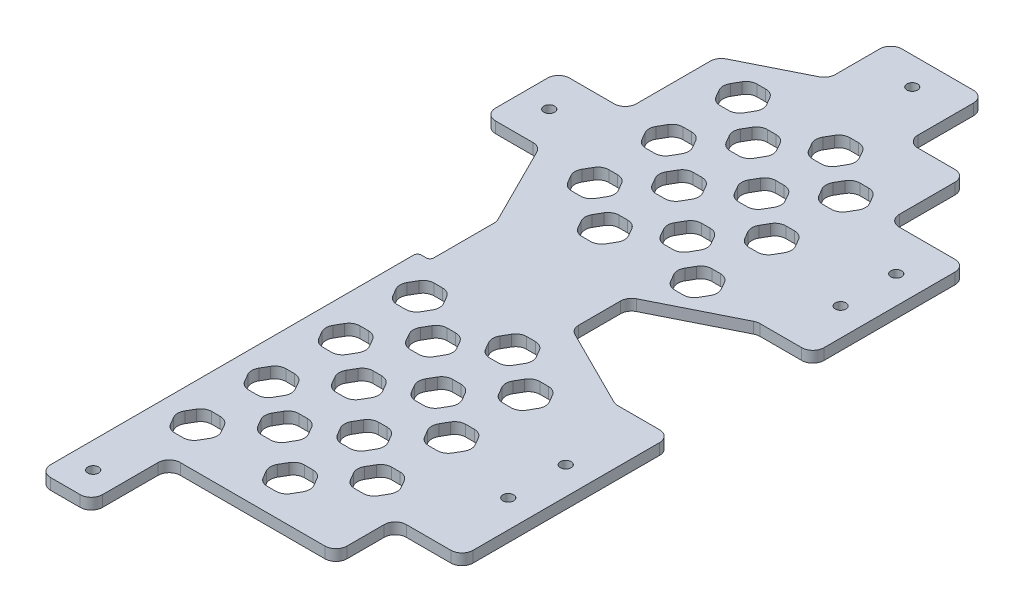
SolidWorks part; units mm, degrees
material "轻木"
ref_plane "前视基准面" through (0, 0, 0) normal (0, 0, 1) x (1, 0, 0)
ref_plane "上视基准面" through (0, 0, 0) normal (0, 1, 0) x (1, 0, 0)
ref_plane "右视基准面" through (0, 0, 0) normal (1, 0, 0) x (0, 0, -1)
other "Configuration Table"
sketch "草图1" plane through (0, 0, 0) normal (0, 1, 0) x (1, 0, 0)
  line L0 (-35.15, -92.5) -> (-35.15, 92.5) construction
  line L1 (-50.15, -107.5) -> (50.15, -107.5) construction
  line L2 (-50.15, -107.5) -> (-50.15, 107.5) construction
  line L3 (-50.15, 107.5) -> (50.15, 107.5) construction
  line L4 (50.15, -107.5) -> (50.15, 107.5) construction
  line L5 (-50.15, -107.5) -> (50.15, 107.5) construction
  line L6 (-50.15, 107.5) -> (50.15, -107.5) construction
  line L7 (-35.15, 92.5) -> (35.15, 92.5) construction
  line L8 (35.15, -92.5) -> (35.15, 92.5) construction
  line L9 (-35.15, -92.5) -> (35.15, -92.5) construction
  line L10 (-29.85, -107.5) -> (-29.85, -2.5) construction
  line L11 (-9.85, -92.5) -> (-9.85, -107.5) construction
  line L12 (-29.85, -2.5) -> (-25.15, -2.5) construction
  line L13 (-25.15, -2.5) -> (-25.15, 12.5) construction
  line L14 (-35.15, 32.5) -> (-50.15, 32.5) construction
  line L15 (-25.15, 12.5) -> (-35.15, 32.5) construction
  line L16 (15.15, 12.5) -> (15.15, -2.5) construction
  line L17 (15.15, -2.5) -> (35.15, -12.5) construction
  line L18 (35.15, -12.5) -> (50.15, -12.5) construction
  line L19 (15.15, 12.5) -> (35.15, 22.5) construction
  line L20 (35.15, 22.5) -> (50.15, 22.5) construction
  line L21 (-54.2695, 5) -> (53.0339, 5) construction
  line L22 (16.15, 107.5) -> (16.15, 92.5) construction
  line L23 (35.15, 68.5) -> (50.15, 68.5) construction
  line L24 (50.15, 65.5) -> (29.15, 65.5)
  line L25 (-50.15, 82.5) -> (-35.15, 82.5) construction
  line L26 (-35.15, 82.5) -> (-15.15, 92.5) construction
  line L27 (35.15, -73.5) -> (50.15, -73.5) construction
  line L28 (-12.85, -86.5) -> (-12.85, -107.5)
  line L29 (-12.85, -107.5) -> (-26.85, -107.5)
  line L30 (-26.85, -107.5) -> (-26.85, -5.5)
  line L31 (-26.85, -5.5) -> (-23.4729, -5.5)
  line L32 (-23.4729, -5.5) -> (-23.4729, 12.5)
  line L33 (-23.4729, 12.5) -> (-35.15, 35.8541)
  line L34 (-35.15, 35.8541) -> (-50.15, 35.8541)
  line L35 (-50.15, 35.8541) -> (-50.15, 55.8541)
  line L36 (-50.15, 55.8541) -> (-32.15, 55.8541)
  line L39 (-12.15, 90.6459) -> (-12.15, 107.5)
  line L40 (-12.15, 107.5) -> (13.15, 107.5)
  line L41 (13.15, 107.5) -> (13.15, 86.5)
  line L44 (50.15, 65.5) -> (50.15, 24.1771)
  line L45 (50.15, 24.1771) -> (35.15, 24.1771)
  line L46 (-25.15, 12.5) -> (15.15, 12.5) construction
  line L47 (-25.15, -2.5) -> (15.15, -2.5) construction
  line L48 (35.15, 24.1771) -> (11.7959, 12.5)
  line L49 (11.7959, 12.5) -> (11.7959, -2.5)
  line L50 (11.7959, -2.5) -> (35.15, -14.1771)
  line L51 (35.15, -14.1771) -> (50.15, -14.1771)
  line L52 (50.15, -14.1771) -> (50.15, -70.5)
  line L53 (50.15, -70.5) -> (32.15, -70.5)
  line L54 (32.15, -70.5) -> (32.15, -86.5)
  line L55 (32.15, -86.5) -> (-12.85, -86.5)
  line L56 (-15.15, 92.5) -> (-15.15, 107.5) construction
  line L57 (-32.15, 55.8541) -> (-32.15, 80.6459)
  line L58 (-32.15, 80.6459) -> (-12.15, 90.6459)
  line L59 (29.15, 65.5) -> (29.15, 86.5)
  line L60 (29.15, 86.5) -> (13.15, 86.5)
  point P0 (0, 0)
  dimension "D1" = 215
  dimension "D2" = 100.3
  dimension "D4" = 105
  dimension "D5" = 5.3
  dimension "D6" = 20
  dimension "D7" = 4.7
  dimension "D8" = 35
  dimension "D9" = 15
  dimension "D10" = 35
  dimension "D11" = 15
  dimension "D12" = 20
  dimension "D13" = 7.5
  dimension "D14" = 19
  dimension "D15" = 25
  dimension "D16" = 20
  dimension "D17" = 19
  dimension "D18" = 3
  dimension "D19" = 3
  dimension "D20" = 6
  dimension "D21" = 3
  dimension "D22" = 3
  dimension "D23" = 3
  dimension "D24" = 3
  dimension "D25" = 3
  dimension "D26" = 24
  dimension "D27" = 3
  dimension "D28" = 3
  dimension "D29" = 3
  dimension "D30" = 20
  dimension "D31" = 3
  dimension "D32" = 6
  dimension "D33" = 3
  dimension "D34" = 6
  dimension "D3" = 15
extrude "凸台-拉伸1" add sketch "草图1" along normal blind 3
fillet "圆角1" radius 3 25 edges at (32.15, 1.5, 70.5) (-12.85, 1.5, 86.5) (-12.85, 1.5, 107.5) (-26.85, 1.5, 107.5) (-23.4729, 1.5, -12.5) (-35.15, 1.5, -35.8541) (-50.15, 1.5, -35.8541) (-50.15, 1.5, -55.8541) (-12.15, 1.5, -107.5) (13.15, 1.5, -107.5) (50.15, 1.5, -24.1771) (35.15, 1.5, -24.1771) (11.7959, 1.5, -12.5) (11.7959, 1.5, 2.5) (35.15, 1.5, 14.1771) (50.15, 1.5, 14.1771) (32.15, 1.5, 86.5) (50.15, 1.5, 70.5) (29.15, 1.5, -86.5) (50.15, 1.5, -65.5) (-32.15, 1.5, -55.8541) (-32.15, 1.5, -80.6459) (-12.15, 1.5, -90.6459) (13.15, 1.5, -86.5) (29.15, 1.5, -65.5)
fillet "圆角2" radius 1 2 edges at (-26.85, 1.5, 5.5) (-23.4729, 1.5, 5.5)
sketch "草图2" plane through (0, 3, 0) normal (0, 1, 0) x (1, 0, 0)
  line L0 (-27.2327, 100) -> (45.5671, 100) construction
  line L1 (-42.65, 71.8095) -> (-42.65, -83.5842) construction
  line L2 (42.65, 78.6701) -> (42.65, -87.3285) construction
  line L3 (-44.3254, -100) -> (0, -100) construction
  line L4 (-23.85, -107.5) -> (-15.85, -107.5) construction
  line L5 (50.15, -67.5) -> (50.15, -17.1771) construction
  line L6 (-50.15, 52.8541) -> (-50.15, 38.8541) construction
  line L7 (10.15, 107.5) -> (-9.15, 107.5) construction
  line L8 (-26.85, -6.5) -> (-26.85, -104.5) construction
  line L9 (35.15, -70.5) -> (47.15, -70.5) construction
  line L10 (35.8582, 24.1771) -> (47.15, 24.1771) construction
  line L11 (-47.15, 35.8541) -> (-37.0041, 35.8541) construction
  line L12 (13.15, 89.5) -> (13.15, 104.5) construction
  circle A0 centre (-19.85, -100) radius 1.45
  circle A1 centre (42.65, -50.5) radius 1.45
  circle A2 centre (42.65, -35) radius 1.45
  circle A3 centre (-42.65, 45.8541) radius 1.45
  circle A4 centre (1.15, 100) radius 1.45
  circle A5 centre (42.65, 54.1771) radius 1.45
  circle A6 centre (42.65, 39.1771) radius 1.45
  dimension "D5" = 2.9
  dimension "D6" = 7
  dimension "D7" = 20
  dimension "D8" = 15.5
  dimension "D9" = 15
  dimension "D10" = 15
  dimension "D12" = 12
  dimension "D1" = 7.5
  dimension "D2" = 7.5
  dimension "D3" = 7.5
  dimension "D4" = 7.5
  dimension "D11" = 10
extrude "切除-拉伸1" cut sketch "草图2" against normal through all
sketch "草图3" plane through (0, 3, 0) normal (0, 1, 0) x (1, 0, 0)
  line L0 (11.4836, 74.7429) -> (8.5968, 79.7429)
  line L1 (-13.5164, 74.7429) -> (-16.4032, 79.7429)
  line L2 (-16.4032, 79.7429) -> (-22.1767, 79.7429)
  line L3 (-22.1767, 79.7429) -> (-25.0634, 74.7429)
  line L4 (-25.0634, 74.7429) -> (-22.1767, 69.7429)
  line L5 (-22.1767, 69.7429) -> (-16.4032, 69.7429)
  line L6 (-16.4032, 69.7429) -> (-13.5164, 74.7429)
  line L7 (-1.527, 65.5092) -> (-4.4137, 70.5092)
  line L8 (-4.4137, 70.5092) -> (-10.1872, 70.5092)
  line L9 (-10.1872, 70.5092) -> (-13.074, 65.5092)
  line L10 (-13.074, 65.5092) -> (-10.1872, 60.5092)
  line L11 (-10.1872, 60.5092) -> (-4.4137, 60.5092)
  line L12 (-4.4137, 60.5092) -> (-1.527, 65.5092)
  line L13 (8.5968, 79.7429) -> (2.8233, 79.7429)
  line L14 (2.8233, 79.7429) -> (-0.0634, 74.7429)
  line L15 (-0.0634, 74.7429) -> (2.8233, 69.7429)
  line L16 (2.8233, 69.7429) -> (8.5968, 69.7429)
  line L17 (8.5968, 69.7429) -> (11.4836, 74.7429)
  line L18 (23.473, 65.5092) -> (20.5863, 70.5092)
  line L19 (20.5863, 70.5092) -> (14.8128, 70.5092)
  line L20 (14.8128, 70.5092) -> (11.926, 65.5092)
  line L21 (11.926, 65.5092) -> (14.8128, 60.5092)
  line L22 (14.8128, 60.5092) -> (20.5863, 60.5092)
  line L23 (20.5863, 60.5092) -> (23.473, 65.5092)
  line L24 (11.4836, 54.7429) -> (8.5968, 59.7429)
  line L25 (8.5968, 59.7429) -> (2.8233, 59.7429)
  line L26 (2.8233, 59.7429) -> (-0.0634, 54.7429)
  line L27 (-0.0634, 54.7429) -> (2.8233, 49.7429)
  line L28 (2.8233, 49.7429) -> (8.5968, 49.7429)
  line L29 (8.5968, 49.7429) -> (11.4836, 54.7429)
  line L30 (23.473, 45.5092) -> (20.5863, 50.5092)
  line L31 (20.5863, 50.5092) -> (14.8128, 50.5092)
  line L32 (14.8128, 50.5092) -> (11.926, 45.5092)
  line L33 (11.926, 45.5092) -> (14.8128, 40.5092)
  line L34 (14.8128, 40.5092) -> (20.5863, 40.5092)
  line L35 (20.5863, 40.5092) -> (23.473, 45.5092)
  line L36 (11.4836, 34.7429) -> (8.5968, 39.7429)
  line L37 (8.5968, 39.7429) -> (2.8233, 39.7429)
  line L38 (2.8233, 39.7429) -> (-0.0634, 34.7429)
  line L39 (-0.0634, 34.7429) -> (2.8233, 29.7429)
  line L40 (2.8233, 29.7429) -> (8.5968, 29.7429)
  line L41 (8.5968, 29.7429) -> (11.4836, 34.7429)
  line L42 (23.473, 25.5092) -> (20.5863, 30.5092)
  line L43 (20.5863, 30.5092) -> (14.8128, 30.5092)
  line L44 (14.8128, 30.5092) -> (11.926, 25.5092)
  line L45 (11.926, 25.5092) -> (14.8128, 20.5092)
  line L46 (14.8128, 20.5092) -> (20.5863, 20.5092)
  line L47 (20.5863, 20.5092) -> (23.473, 25.5092)
  line L48 (-13.5164, 54.7429) -> (-16.4032, 59.7429)
  line L49 (-16.4032, 59.7429) -> (-22.1767, 59.7429)
  line L50 (-22.1767, 59.7429) -> (-25.0634, 54.7429)
  line L51 (-25.0634, 54.7429) -> (-22.1767, 49.7429)
  line L52 (-22.1767, 49.7429) -> (-16.4032, 49.7429)
  line L53 (-16.4032, 49.7429) -> (-13.5164, 54.7429)
  line L54 (-1.527, 45.5092) -> (-4.4137, 50.5092)
  line L55 (-4.4137, 50.5092) -> (-10.1872, 50.5092)
  line L56 (-10.1872, 50.5092) -> (-13.074, 45.5092)
  line L57 (-13.074, 45.5092) -> (-10.1872, 40.5092)
  line L58 (-10.1872, 40.5092) -> (-4.4137, 40.5092)
  line L59 (-4.4137, 40.5092) -> (-1.527, 45.5092)
  line L60 (-13.5164, 34.7429) -> (-16.4032, 39.7429)
  line L61 (-16.4032, 39.7429) -> (-22.1767, 39.7429)
  line L62 (-22.1767, 39.7429) -> (-25.0634, 34.7429)
  line L63 (-25.0634, 34.7429) -> (-22.1767, 29.7429)
  line L64 (-22.1767, 29.7429) -> (-16.4032, 29.7429)
  line L65 (-16.4032, 29.7429) -> (-13.5164, 34.7429)
  line L66 (-1.527, 25.5092) -> (-4.4137, 30.5092)
  line L67 (-4.4137, 30.5092) -> (-10.1872, 30.5092)
  line L68 (-10.1872, 30.5092) -> (-13.074, 25.5092)
  line L69 (-13.074, 25.5092) -> (-10.1872, 20.5092)
  line L70 (-10.1872, 20.5092) -> (-4.4137, 20.5092)
  line L71 (-4.4137, 20.5092) -> (-1.527, 25.5092)
  line L84 (14.3703, -15.3234) -> (11.4836, -10.3234)
  line L85 (-10.6297, -15.3234) -> (-13.5164, -10.3234)
  line L86 (-13.5164, -10.3234) -> (-19.2899, -10.3234)
  line L87 (-19.2899, -10.3234) -> (-22.1767, -15.3234)
  line L88 (-22.1767, -15.3234) -> (-19.2899, -20.3234)
  line L89 (-19.2899, -20.3234) -> (-13.5164, -20.3234)
  line L90 (-13.5164, -20.3234) -> (-10.6297, -15.3234)
  line L91 (1.6479, -24.0581) -> (-1.2389, -19.0581)
  line L92 (-1.2389, -19.0581) -> (-7.0124, -19.0581)
  line L93 (-7.0124, -19.0581) -> (-9.8991, -24.0581)
  line L94 (-9.8991, -24.0581) -> (-7.0124, -29.0581)
  line L95 (-7.0124, -29.0581) -> (-1.2389, -29.0581)
  line L96 (-1.2389, -29.0581) -> (1.6479, -24.0581)
  line L97 (11.4836, -10.3234) -> (5.7101, -10.3234)
  line L98 (5.7101, -10.3234) -> (2.8233, -15.3234)
  line L99 (2.8233, -15.3234) -> (5.7101, -20.3234)
  line L100 (5.7101, -20.3234) -> (11.4836, -20.3234)
  line L101 (11.4836, -20.3234) -> (14.3703, -15.3234)
  line L102 (26.6479, -24.0581) -> (23.7611, -19.0581)
  line L103 (23.7611, -19.0581) -> (17.9876, -19.0581)
  line L104 (17.9876, -19.0581) -> (15.1009, -24.0581)
  line L105 (15.1009, -24.0581) -> (17.9876, -29.0581)
  line L106 (17.9876, -29.0581) -> (23.7611, -29.0581)
  line L107 (23.7611, -29.0581) -> (26.6479, -24.0581)
  line L108 (14.3703, -35.3234) -> (11.4836, -30.3234)
  line L109 (11.4836, -30.3234) -> (5.7101, -30.3234)
  line L110 (5.7101, -30.3234) -> (2.8233, -35.3234)
  line L111 (2.8233, -35.3234) -> (5.7101, -40.3234)
  line L112 (5.7101, -40.3234) -> (11.4836, -40.3234)
  line L113 (11.4836, -40.3234) -> (14.3703, -35.3234)
  line L114 (26.6479, -44.0581) -> (23.7611, -39.0581)
  line L115 (23.7611, -39.0581) -> (17.9876, -39.0581)
  line L116 (17.9876, -39.0581) -> (15.1009, -44.0581)
  line L117 (15.1009, -44.0581) -> (17.9876, -49.0581)
  line L118 (17.9876, -49.0581) -> (23.7611, -49.0581)
  line L119 (23.7611, -49.0581) -> (26.6479, -44.0581)
  line L120 (14.3703, -55.3234) -> (11.4836, -50.3234)
  line L121 (11.4836, -50.3234) -> (5.7101, -50.3234)
  line L122 (5.7101, -50.3234) -> (2.8233, -55.3234)
  line L123 (2.8233, -55.3234) -> (5.7101, -60.3234)
  line L124 (5.7101, -60.3234) -> (11.4836, -60.3234)
  line L125 (11.4836, -60.3234) -> (14.3703, -55.3234)
  line L126 (26.6479, -64.0581) -> (23.7611, -59.0581)
  line L127 (23.7611, -59.0581) -> (17.9876, -59.0581)
  line L128 (17.9876, -59.0581) -> (15.1009, -64.0581)
  line L129 (15.1009, -64.0581) -> (17.9876, -69.0581)
  line L130 (17.9876, -69.0581) -> (23.7611, -69.0581)
  line L131 (23.7611, -69.0581) -> (26.6479, -64.0581)
  line L132 (14.3703, -75.3234) -> (11.4836, -70.3234)
  line L133 (11.4836, -70.3234) -> (5.7101, -70.3234)
  line L134 (5.7101, -70.3234) -> (2.8233, -75.3234)
  line L135 (2.8233, -75.3234) -> (5.7101, -80.3234)
  line L136 (5.7101, -80.3234) -> (11.4836, -80.3234)
  line L137 (11.4836, -80.3234) -> (14.3703, -75.3234)
  line L144 (-10.6297, -35.3234) -> (-13.5164, -30.3234)
  line L145 (-13.5164, -30.3234) -> (-19.2899, -30.3234)
  line L146 (-19.2899, -30.3234) -> (-22.1767, -35.3234)
  line L147 (-22.1767, -35.3234) -> (-19.2899, -40.3234)
  line L148 (-19.2899, -40.3234) -> (-13.5164, -40.3234)
  line L149 (-13.5164, -40.3234) -> (-10.6297, -35.3234)
  line L150 (1.6479, -44.0581) -> (-1.2389, -39.0581)
  line L151 (-1.2389, -39.0581) -> (-7.0124, -39.0581)
  line L152 (-7.0124, -39.0581) -> (-9.8991, -44.0581)
  line L153 (-9.8991, -44.0581) -> (-7.0124, -49.0581)
  line L154 (-7.0124, -49.0581) -> (-1.2389, -49.0581)
  line L155 (-1.2389, -49.0581) -> (1.6479, -44.0581)
  line L156 (-10.6297, -55.3234) -> (-13.5164, -50.3234)
  line L157 (-13.5164, -50.3234) -> (-19.2899, -50.3234)
  line L158 (-19.2899, -50.3234) -> (-22.1767, -55.3234)
  line L159 (-22.1767, -55.3234) -> (-19.2899, -60.3234)
  line L160 (-19.2899, -60.3234) -> (-13.5164, -60.3234)
  line L161 (-13.5164, -60.3234) -> (-10.6297, -55.3234)
  line L162 (1.6479, -64.0581) -> (-1.2389, -59.0581)
  line L163 (-1.2389, -59.0581) -> (-7.0124, -59.0581)
  line L164 (-7.0124, -59.0581) -> (-9.8991, -64.0581)
  line L165 (-9.8991, -64.0581) -> (-7.0124, -69.0581)
  line L166 (-7.0124, -69.0581) -> (-1.2389, -69.0581)
  line L167 (-1.2389, -69.0581) -> (1.6479, -64.0581)
  line L168 (-10.6297, -75.3234) -> (-13.5164, -70.3234)
  line L169 (-13.5164, -70.3234) -> (-19.2899, -70.3234)
  line L170 (-19.2899, -70.3234) -> (-22.1767, -75.3234)
  line L171 (-22.1767, -75.3234) -> (-19.2899, -80.3234)
  line L172 (-19.2899, -80.3234) -> (-13.5164, -80.3234)
  line L173 (-13.5164, -80.3234) -> (-10.6297, -75.3234)
  line L180 (-1.2389, -79.0581) -> (-7.0124, -79.0581) [skipped]
  line L181 (-7.0124, -79.0581) -> (-9.8991, -84.0581) [skipped]
  line L182 (-9.8991, -84.0581) -> (-7.0124, -89.0581) [skipped]
  line L183 (-7.0124, -89.0581) -> (-1.2389, -89.0581) [skipped]
  line L184 (-1.2389, -89.0581) -> (1.6479, -84.0581) [skipped]
  line L185 (1.6479, -84.0581) -> (-1.2389, -79.0581) [skipped]
  line L186 (17.9876, -79.0581) -> (15.1009, -84.0581) [skipped]
  line L187 (23.7611, -79.0581) -> (17.9876, -79.0581) [skipped]
  line L188 (26.6479, -84.0581) -> (23.7611, -79.0581) [skipped]
  line L189 (23.7611, -89.0581) -> (26.6479, -84.0581) [skipped]
  line L190 (17.9876, -89.0581) -> (23.7611, -89.0581) [skipped]
  line L191 (15.1009, -84.0581) -> (17.9876, -89.0581) [skipped]
  circle A0 centre (-19.2899, 74.7429) radius 5 construction
  circle A1 centre (-7.3005, 65.5092) radius 5 construction
  circle A4 centre (-16.4032, -15.3234) radius 5 construction
  circle A5 centre (-4.1256, -24.0581) radius 5 construction
  dimension "D1" = 10
  dimension "D5" = 10
  dimension "D6" = 10
  dimension "D2" = 5
  dimension "D7" = 5
  dimension "D3" = 2
  dimension "D4" = 3
  dimension "D8" = 2
  dimension "D9" = 4
extrude "切除-拉伸2" cut sketch "草图3" against normal through all
fillet "圆角3" radius 3 156 edges at (-22.1767, 1.5, -69.7429) (-25.0634, 1.5, -74.7429) (-22.1767, 1.5, -79.7429) (-16.4032, 1.5, -79.7429) (-13.5164, 1.5, -74.7429) (-16.4032, 1.5, -69.7429) (5.7101, 1.5, 80.3234) (2.8233, 1.5, 75.3234) (5.7101, 1.5, 70.3234) (11.4836, 1.5, 70.3234) (14.3703, 1.5, 75.3234) (11.4836, 1.5, 80.3234) (17.9876, 1.5, 69.0581) (15.1009, 1.5, 64.0581) (17.9876, 1.5, 59.0581) (23.7611, 1.5, 59.0581) (26.6479, 1.5, 64.0581) (23.7611, 1.5, 69.0581) (5.7101, 1.5, 60.3234) (2.8233, 1.5, 55.3234) (5.7101, 1.5, 50.3234) (11.4836, 1.5, 50.3234) (14.3703, 1.5, 55.3234) (11.4836, 1.5, 60.3234) (17.9876, 1.5, 49.0581) (15.1009, 1.5, 44.0581) (17.9876, 1.5, 39.0581) (23.7611, 1.5, 39.0581) (26.6479, 1.5, 44.0581) (23.7611, 1.5, 49.0581) (-19.2899, 1.5, 40.3234) (-22.1767, 1.5, 35.3234) (-19.2899, 1.5, 30.3234) (-13.5164, 1.5, 30.3234) (-10.6297, 1.5, 35.3234) (-13.5164, 1.5, 40.3234) (-7.0124, 1.5, 49.0581) (-9.8991, 1.5, 44.0581) (-7.0124, 1.5, 39.0581) (-1.2389, 1.5, 39.0581) (1.6479, 1.5, 44.0581) (-1.2389, 1.5, 49.0581) (-19.2899, 1.5, 60.3234) (-22.1767, 1.5, 55.3234) (-19.2899, 1.5, 50.3234) (-13.5164, 1.5, 50.3234) (-10.6297, 1.5, 55.3234) (-13.5164, 1.5, 60.3234) (-7.0124, 1.5, 69.0581) (-9.8991, 1.5, 64.0581) (-7.0124, 1.5, 59.0581) (-1.2389, 1.5, 59.0581) (1.6479, 1.5, 64.0581) (-1.2389, 1.5, 69.0581) (-19.2899, 1.5, 80.3234) (-22.1767, 1.5, 75.3234) (-19.2899, 1.5, 70.3234) (-13.5164, 1.5, 70.3234) (-10.6297, 1.5, 75.3234) (-13.5164, 1.5, 80.3234) (14.8128, 1.5, -20.5092) (11.926, 1.5, -25.5092) (14.8128, 1.5, -30.5092) (20.5863, 1.5, -30.5092) (23.473, 1.5, -25.5092) (20.5863, 1.5, -20.5092) (2.8233, 1.5, -29.7429) (-0.0634, 1.5, -34.7429) (2.8233, 1.5, -39.7429) (8.5968, 1.5, -39.7429) (11.4836, 1.5, -34.7429) (8.5968, 1.5, -29.7429) (14.8128, 1.5, -40.5092) (11.926, 1.5, -45.5092) (14.8128, 1.5, -50.5092) (20.5863, 1.5, -50.5092) (23.473, 1.5, -45.5092) (20.5863, 1.5, -40.5092) (2.8233, 1.5, -49.7429) (-0.0634, 1.5, -54.7429) (2.8233, 1.5, -59.7429) (8.5968, 1.5, -59.7429) (11.4836, 1.5, -54.7429) (8.5968, 1.5, -49.7429) (-10.1872, 1.5, -60.5092) (-13.074, 1.5, -65.5092) (-10.1872, 1.5, -70.5092) (-4.4137, 1.5, -70.5092) (-1.527, 1.5, -65.5092) (-4.4137, 1.5, -60.5092) (2.8233, 1.5, -69.7429) (-0.0634, 1.5, -74.7429) (2.8233, 1.5, -79.7429) (11.4836, 1.5, -74.7429) (8.5968, 1.5, -69.7429) (-19.2899, 1.5, 20.3234) (-22.1767, 1.5, 15.3234) (-19.2899, 1.5, 10.3234) (-13.5164, 1.5, 10.3234) (-10.6297, 1.5, 15.3234) (-13.5164, 1.5, 20.3234) (14.8128, 1.5, -60.5092) (11.926, 1.5, -65.5092) (14.8128, 1.5, -70.5092) (23.473, 1.5, -65.5092) (20.5863, 1.5, -60.5092) (-22.1767, 1.5, -49.7429) (-25.0634, 1.5, -54.7429) (-22.1767, 1.5, -59.7429) (-16.4032, 1.5, -59.7429) (-13.5164, 1.5, -54.7429) (-16.4032, 1.5, -49.7429) (-10.1872, 1.5, -40.5092) (-13.074, 1.5, -45.5092) (-10.1872, 1.5, -50.5092) (-4.4137, 1.5, -50.5092) (-1.527, 1.5, -45.5092) (-4.4137, 1.5, -40.5092) (-22.1767, 1.5, -29.7429) (-25.0634, 1.5, -34.7429) (-22.1767, 1.5, -39.7429) (-16.4032, 1.5, -39.7429) (-13.5164, 1.5, -34.7429) (-16.4032, 1.5, -29.7429) (-10.1872, 1.5, -20.5092) (-13.074, 1.5, -25.5092) (-10.1872, 1.5, -30.5092) (-4.4137, 1.5, -30.5092) (-1.527, 1.5, -25.5092) (-4.4137, 1.5, -20.5092) (5.7101, 1.5, 40.3234) (2.8233, 1.5, 35.3234) (5.7101, 1.5, 30.3234) (11.4836, 1.5, 30.3234) (14.3703, 1.5, 35.3234) (11.4836, 1.5, 40.3234) (17.9876, 1.5, 29.0581) (15.1009, 1.5, 24.0581) (17.9876, 1.5, 19.0581) (23.7611, 1.5, 19.0581) (26.6479, 1.5, 24.0581) (23.7611, 1.5, 29.0581) (5.7101, 1.5, 20.3234) (2.8233, 1.5, 15.3234) (5.7101, 1.5, 10.3234) (11.4836, 1.5, 10.3234) (14.3703, 1.5, 15.3234) (11.4836, 1.5, 20.3234) (-7.0124, 1.5, 29.0581) (-9.8991, 1.5, 24.0581) (-7.0124, 1.5, 19.0581) (-1.2389, 1.5, 19.0581) (1.6479, 1.5, 24.0581) (-1.2389, 1.5, 29.0581) (20.5863, 1.5, -70.5092) (8.5968, 1.5, -79.7429)
